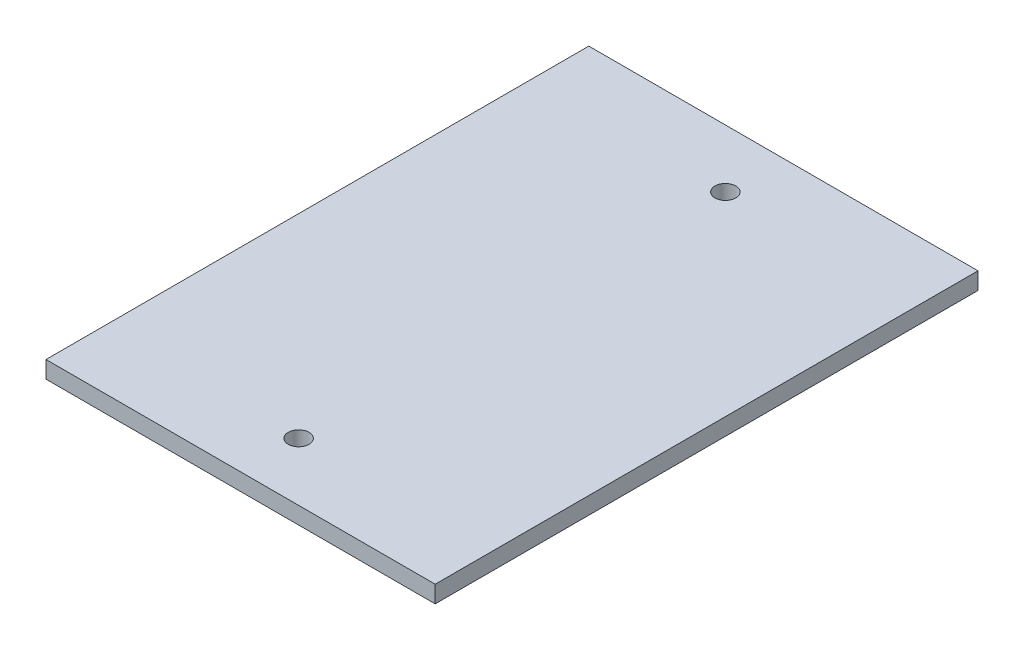
SolidWorks part; units mm, degrees
ref_plane "Front Plane" through (0, 0, 0) normal (0, 0, 1) x (1, 0, 0)
ref_plane "Top Plane" through (0, 0, 0) normal (0, 1, 0) x (1, 0, 0)
ref_plane "Right Plane" through (0, 0, 0) normal (1, 0, 0) x (0, 0, -1)
sketch "Sketch1" plane through (0, 0, 0) normal (0, 1, 0) x (1, 0, 0)
  line L1 (-28.956, -40.386) -> (28.956, -40.386)
  line L2 (-28.956, -40.386) -> (-28.956, 40.386)
  line L3 (-28.956, 40.386) -> (28.956, 40.386)
  line L4 (28.956, -40.386) -> (28.956, 40.386)
  line L5 (-28.956, -40.386) -> (28.956, 40.386) construction
  line L6 (-28.956, 40.386) -> (28.956, -40.386) construction
  point P0 (0, 0)
  dimension "D1" = 80.772
  dimension "D2" = 57.912
extrude "Boss-Extrude1" add sketch "Sketch1" along normal blind 2.54
sketch "Sketch3" plane through (0, 2.54, 0) normal (0, 1, 0) x (1, 0, 0)
  line L0 (8.636, -31.496) -> (23.876, -31.496) construction
  line L1 (8.636, -31.496) -> (8.636, 9.144) construction
  line L2 (8.636, 9.144) -> (23.876, 9.144) construction
  line L3 (28.956, -40.386) -> (28.956, 40.386) construction
  line L4 (-28.956, -40.386) -> (28.956, -40.386) construction
  circle A0 centre (8.636, -31.496) radius 0.9
  circle A1 centre (23.876, -31.496) radius 0.9
  circle A2 centre (8.636, 9.144) radius 0.9 construction
  circle A3 centre (23.876, 9.144) radius 0.9 construction
  dimension "D1" = 1.8
  dimension "D2" = 40.64
  dimension "D3" = 15.24
  dimension "D4" = 5.08
  dimension "D5" = 8.89
extrude "Boss-Extrude3" [suppressed] add sketch "Sketch3" along normal blind 12.7
sketch "Sketch4" plane through (-28.956, 0, 0) normal (-1, 0, 0) x (0, 0, 1)
  line L0 (-10.883, 2.54) -> (-10.883, 16.2343)
  line L1 (-40.386, 2.54) -> (40.386, 2.54) construction
  line L2 (-10.883, 16.2343) -> (-8.3278, 16.2343)
  line L3 (-8.3278, 16.2343) -> (-8.3278, 8.89)
  line L4 (-8.3278, 8.89) -> (10.7222, 8.89)
  line L5 (10.7222, 8.89) -> (10.7222, 16.2343)
  line L6 (10.7222, 16.2343) -> (13.2773, 16.2343)
  line L7 (13.2773, 16.2343) -> (13.2773, 2.54)
  line L9 (13.2773, 2.54) -> (-10.883, 2.54)
  dimension "D1" = 19.05
  dimension "D2" = 6.35
extrude "Boss-Extrude4" [suppressed] add sketch "Sketch4" against normal blind 12.7 from offset 5.08 offset against normal yes
sketch "Sketch5" plane through (0, 2.54, 0) normal (0, 1, 0) x (1, 0, 0)
  line L0 (0, 31.75) -> (0, 40.386) construction
  line L1 (28.956, 40.386) -> (-28.956, 40.386) construction
  line L2 (0, -31.75) -> (0, -40.386) construction
  line L3 (-28.956, -40.386) -> (28.956, -40.386) construction
  circle A0 centre (0, -31.75) radius 1.55
  circle A1 centre (0, 31.75) radius 1.55
  circle A2 centre (0, -31.75) radius 1.35 construction
  dimension "D1" = 3.1
extrude "Cut-Extrude1" cut sketch "Sketch5" against normal blind 2.54
